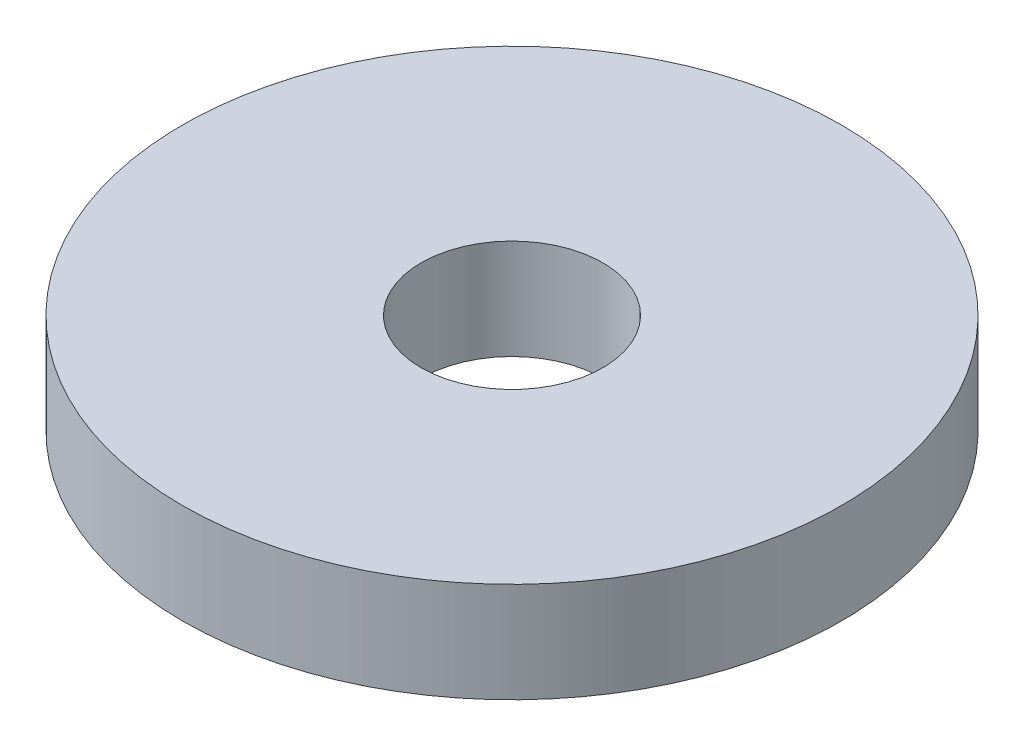
SolidWorks part; units mm, degrees
ref_plane "Front Plane" through (0, 0, 0) normal (0, 0, 1) x (1, 0, 0)
ref_plane "Top Plane" through (0, 0, 0) normal (0, 1, 0) x (1, 0, 0)
ref_plane "Right Plane" through (0, 0, 0) normal (1, 0, 0) x (0, 0, -1)
sketch "Sketch1" plane through (0, 0, 0) normal (0, 1, 0) x (1, 0, 0)
  circle A0 centre (0, 0) radius 72.5
  dimension "FLANGE_OD" = 145
extrude "Boss-Extrude1" add sketch "Sketch1" along normal blind 22
sketch "Sketch2" plane through (0, 0, 0) normal (0, 1, 0) x (1, 0, 0)
  circle A0 centre (0, 0) radius 20
  dimension "BORE_D" = 40
extrude "Cut-Extrude1" cut sketch "Sketch2" along normal through all
sketch "Sketch3" plane through (0, 22, 0) normal (0, 1, 0) x (1, 0, 0)
  circle A0 centre (0, 0) radius 16.8043 construction
  circle A1 centre (-16.8043, 0) radius 2.6473
  dimension "BOLT_D" = 5.2946
  dimension "BOLT_PCD" = 33.6086
extrude "Cut-Extrude2" cut sketch "Sketch3" against normal blind 17.3222 rebuild error yes
pattern_circular "CirPattern1" count 6 over 360 rebuild error yes
